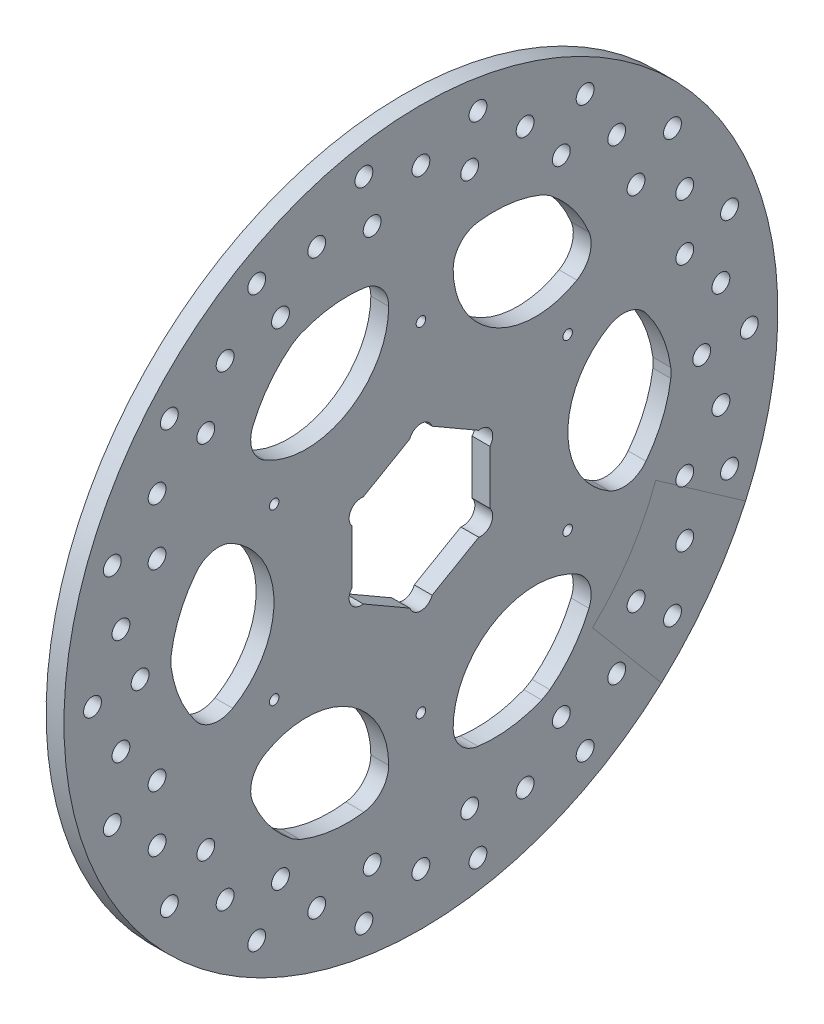
SolidWorks part; units mm, degrees
material "Gray Cast Iron (w/YS)"
ref_plane "X-Y Datum" through (0, 0, 0) normal (0, 0, 1) x (1, 0, 0)
ref_plane "X-Z Datum" through (0, 0, 0) normal (0, 1, 0) x (1, 0, 0)
ref_plane "Y-Z Datum" through (0, 0, 0) normal (1, 0, 0) x (0, 0, -1)
sketch "Sketch1" plane through (0, 0, 0) normal (1, 0, 0) x (0, 0, -1)
  circle A0 centre (0, 0) radius 95.25
  circle A1 centre (0, 0) radius 66.675
  dimension "D1" = 190.5
  dimension "D2" = 133.35
extrude "Main Rotor" add sketch "Sketch1" along normal blind 4.7625
sketch "Sketch2" plane through (4.7625, 0, 0) normal (1, 0, 0) x (0, 0, -1)
  line L0 (0, 0) -> (-50000, 0) construction
  line L1 (0, 0) -> (-93.8029, 16.54) construction
  line L4 (-82.3453, 29.9712) -> (-70.4112, 25.6276) construction
  circle A2 centre (0, 0) radius 95.25 construction
  circle A72 centre (-80.0452, 14.1141) radius 2.3813
  circle A73 centre (0, 0) radius 66.675 construction
  circle A74 centre (-82.3453, 29.9712) radius 2.3812
  circle A75 centre (-70.4112, 25.6276) radius 2.3813
  circle A76 centre (0, 0) radius 95.25 construction
  circle A77 centre (-70.3905, 40.64) radius 2.3812
  circle A78 centre (-67.1285, 56.3275) radius 2.3813
  circle A79 centre (0, 0) radius 66.675 construction
  circle A80 centre (-57.3997, 48.1641) radius 2.3813
  circle A81 centre (-52.2458, 62.2641) radius 2.3813
  circle A82 centre (-87.63, 0) radius 2.3813
  circle A83 centre (-43.815, 75.8898) radius 2.3812
  circle A84 centre (-37.465, 64.8913) radius 2.3813
  circle A85 centre (-74.93, 0) radius 2.3813
  circle A86 centre (-27.7994, 76.3782) radius 2.3812
  circle A87 centre (-15.2168, 86.2987) radius 2.3813
  circle A88 centre (-13.0115, 73.7916) radius 2.3813
  circle A89 centre (0, 81.28) radius 2.3813
  circle A90 centre (15.2168, 86.2987) radius 2.3813
  circle A91 centre (13.0115, 73.7916) radius 2.3813
  circle A92 centre (27.7994, 76.3782) radius 2.3813
  circle A93 centre (43.815, 75.8898) radius 2.3813
  circle A94 centre (37.465, 64.8913) radius 2.3813
  circle A95 centre (52.2458, 62.2641) radius 2.3813
  circle A96 centre (67.1285, 56.3275) radius 2.3813
  circle A97 centre (57.3997, 48.1641) radius 2.3813
  circle A98 centre (70.3905, 40.64) radius 2.3812
  circle A99 centre (82.3453, 29.9712) radius 2.3813
  circle A100 centre (70.4112, 25.6276) radius 2.3813
  circle A101 centre (80.0452, 14.1141) radius 2.3813
  circle A102 centre (87.63, 0) radius 2.3813
  circle A103 centre (74.93, 0) radius 2.3813
  circle A104 centre (80.0452, -14.1141) radius 2.3813
  circle A105 centre (82.3453, -29.9712) radius 2.3812
  circle A106 centre (70.4112, -25.6276) radius 2.3812
  circle A107 centre (70.3905, -40.64) radius 2.3813
  circle A108 centre (67.1285, -56.3275) radius 2.3812
  circle A109 centre (57.3997, -48.1641) radius 2.3813
  circle A110 centre (52.2458, -62.2641) radius 2.3812
  circle A111 centre (43.815, -75.8898) radius 2.3813
  circle A112 centre (37.465, -64.8913) radius 2.3813
  circle A113 centre (27.7994, -76.3782) radius 2.3813
  circle A114 centre (15.2168, -86.2987) radius 2.3813
  circle A115 centre (13.0115, -73.7916) radius 2.3812
  circle A116 centre (0, -81.28) radius 2.3812
  circle A117 centre (-15.2168, -86.2987) radius 2.3813
  circle A118 centre (-13.0115, -73.7916) radius 2.3813
  circle A119 centre (-27.7994, -76.3782) radius 2.3812
  circle A120 centre (-43.815, -75.8898) radius 2.3813
  circle A121 centre (-37.465, -64.8913) radius 2.3813
  circle A122 centre (-52.2458, -62.2641) radius 2.3813
  circle A123 centre (-67.1285, -56.3275) radius 2.3813
  circle A124 centre (-57.3997, -48.1641) radius 2.3813
  circle A125 centre (-70.3905, -40.64) radius 2.3813
  circle A126 centre (-82.3453, -29.9712) radius 2.3813
  circle A127 centre (-70.4112, -25.6276) radius 2.3813
  circle A128 centre (-80.0452, -14.1141) radius 2.3813
  point P109 (0, 0)
  dimension "D1" = 4.7625
  dimension "D2" = 12.7
  dimension "D3" = 10
  dimension "D5" = 81.28
  dimension "D4" = 87.63
  dimension "D6" = 18
extrude "Cut Slots" cut sketch "Sketch2" against normal through all
sketch "Sketch3" plane through (4.7625, 0, 0) normal (1, 0, 0) x (0, 0, -1)
  line L0 (0, 0) -> (-43301.2702, 25000) construction
  line L1 (0, 21.2491) -> (-18.4023, 10.6246)
  line L2 (-18.4023, 10.6246) -> (-18.4023, -10.6246)
  line L3 (-18.4023, -10.6246) -> (0, -21.2491)
  line L4 (0, -21.2491) -> (18.4023, -10.6246)
  line L5 (18.4023, -10.6246) -> (18.4023, 10.6246)
  line L6 (18.4023, 10.6246) -> (0, 21.2491)
  line L7 (0, 0) -> (43301.2702, 25000) construction
  line L8 (0, 0) -> (0, 50000) construction
  line L12 (9.525, -59.2994) -> (-9.525, -59.2994) construction
  line L17 (-30.6007, -53.002) -> (24969.3838, 43248.2414) construction
  line L18 (-60.783, 0) -> (49939.217, 0) construction
  line L19 (0, 0) -> (-25000, 43301.2702) construction
  arc A0 (8.6043, -53.0208) -> (15.2264, -60.5686) centre (16.2243, -53.0143) ccw
  circle A1 centre (0, 0) radius 66.675 construction
  arc A7 (-15.2264, -60.5686) -> (-32.2316, -58.3668) centre (-19.5921, -27.5182) cw
  arc A10 (15.2264, -60.5686) -> (32.2316, -58.3668) centre (19.5921, -27.5182) ccw
  arc A19 (-19.6024, -33.9524) -> (-8.6043, -53.0208) centre (-30.6006, -53.0019) cw
  arc A25 (41.6152, -33.9619) -> (44.8408, -43.4707) centre (37.7996, -40.5577) cw
  arc A26 (34.4313, -57.0968) -> (66.6629, -1.27) centre (0, 0) ccw
  arc A27 (50.2195, -19.0589) -> (60.0672, -17.0979) centre (54.0238, -12.4565) ccw
  arc A28 (19.6024, -33.9524) -> (8.6043, -53.0208) centre (30.6006, -53.0019) ccw
  arc A29 (60.0672, 17.0979) -> (50.2195, 19.0589) centre (54.0238, 12.4565) ccw
  arc A30 (-44.8408, -43.4707) -> (-34.4313, -57.0968) centre (-14.0354, -30.7264) ccw
  arc A31 (-19.6024, -33.9524) -> (-41.6152, -33.9619) centre (-30.6006, -53.0019) ccw
  arc A32 (-39.2049, 0) -> (-50.2195, -19.0589) centre (-61.2013, 0) cw
  arc A33 (-60.0672, -17.0979) -> (-66.6629, -1.27) centre (-33.6275, 3.2082) cw
  arc A34 (-60.0672, 17.0979) -> (-66.6629, 1.27) centre (-33.6275, -3.2082) ccw
  arc A35 (44.8408, 43.4707) -> (41.6152, 33.9619) centre (37.7996, 40.5577) cw
  arc A36 (-32.2316, -58.3668) -> (32.2316, -58.3668) centre (0, 0) ccw
  arc A37 (15.2264, 60.5686) -> (8.6043, 53.0208) centre (16.2243, 53.0143) ccw
  arc A38 (-8.6043, 53.0208) -> (-15.2264, 60.5686) centre (-16.2243, 53.0143) ccw
  arc A39 (-44.8408, 43.4707) -> (-41.6152, 33.9619) centre (-37.7996, 40.5577) ccw
  arc A40 (-50.2195, 19.0589) -> (-60.0672, 17.0979) centre (-54.0238, 12.4565) ccw
  arc A41 (-50.2195, -19.0589) -> (-60.0672, -17.0979) centre (-54.0238, -12.4565) cw
  arc A42 (-8.6043, -53.0208) -> (-15.2264, -60.5686) centre (-16.2243, -53.0143) cw
  arc A43 (-41.6152, -33.9619) -> (-44.8408, -43.4707) centre (-37.7996, -40.5577) ccw
  arc A44 (-39.2049, 0) -> (-50.2195, 19.0589) centre (-61.2013, 0) ccw
  arc A45 (-19.6025, 33.9524) -> (-41.6152, 33.9619) centre (-30.6007, 53.0019) cw
  arc A46 (-44.8408, 43.4707) -> (-34.4313, 57.0968) centre (-14.0354, 30.7264) cw
  arc A47 (-15.2264, 60.5686) -> (-32.2316, 58.3668) centre (-19.5921, 27.5182) ccw
  arc A48 (-19.6025, 33.9524) -> (-8.6043, 53.0208) centre (-30.6007, 53.0019) ccw
  arc A49 (19.6024, 33.9524) -> (8.6043, 53.0208) centre (30.6006, 53.0019) cw
  arc A50 (15.2264, 60.5686) -> (32.2316, 58.3668) centre (19.5921, 27.5182) cw
  arc A51 (44.8408, 43.4707) -> (34.4313, 57.0968) centre (14.0354, 30.7264) ccw
  arc A52 (19.6024, 33.9524) -> (41.6152, 33.9619) centre (30.6006, 53.0019) ccw
  arc A53 (39.2049, 0) -> (50.2195, 19.0589) centre (61.2013, 0) cw
  arc A54 (60.0672, 17.0979) -> (66.6629, 1.27) centre (33.6275, -3.2082) cw
  arc A55 (60.0672, -17.0979) -> (66.6629, -1.27) centre (33.6275, 3.2082) ccw
  arc A56 (39.2049, 0) -> (50.2195, -19.0589) centre (61.2013, 0) ccw
  arc A57 (19.6024, -33.9524) -> (41.6152, -33.9619) centre (30.6007, -53.0019) cw
  arc A58 (44.8408, -43.4707) -> (34.4313, -57.0968) centre (14.0354, -30.7264) cw
  circle A59 centre (0, 18.4551) radius 3.175
  arc A60 (-66.6629, -1.27) -> (-34.4313, -57.0968) centre (0, 0) ccw
  circle A61 centre (15.9826, 9.2276) radius 3.175
  arc A62 (-34.4313, 57.0968) -> (-66.6629, 1.27) centre (0, 0) ccw
  circle A63 centre (15.9826, -9.2276) radius 3.175
  arc A64 (32.2316, 58.3668) -> (-32.2316, 58.3668) centre (0, 0) ccw
  arc A66 (66.6629, 1.27) -> (34.4313, 57.0968) centre (0, 0) ccw
  circle A68 centre (0, -18.4551) radius 3.175
  circle A69 centre (-15.9826, -9.2276) radius 3.175
  circle A70 centre (-15.9826, 9.2276) radius 3.175
  point P34 (0, -59.2994)
  point P35 (-9.2012, 15.9369)
  point P109 (0, 0)
  point P110 (0, 0)
  point P124 (0, 0)
  dimension "D2" = 42.799
  dimension "D4" = 7.62
  dimension "D7" = 1.27
  dimension "D8" = 33.3375
  dimension "D9" = 21.9964
  dimension "D10" = 6.35
  dimension "D11" = 6.35
  dimension "D12" = 6.35
  dimension "D13" = 6.35
  dimension "D14" = 6.35
  dimension "D15" = 6.35
  dimension "D1" = 36.8046
  dimension "D3" = 6
  dimension "D5" = 2.794
  dimension "D6" = 19.05
  dimension "D16" = 2.794
  dimension "D17" = 2.794
  dimension "D18" = 2.794
  dimension "D19" = 2.794
  dimension "D20" = 2.794
extrude "Boss-Extrude2" add sketch "Sketch3" against normal up to surface (4.7625 mm away) contours A54 A66 A51 A35 A52 A49 A37 A50 A64 A47 A38 A48 A45 A39 A46 A62 A34 A40 A44 A32 A41 A33 A60 A30 A43 A31 A19 A42 A7 A36 A10 A0 A28 A57 A25 A58 A26 A55 A27 A56 A53 A29 A70 L1 A59 L6 A61 L5 A63 L4 region at (4.7625, -59.2833, -9.0788) up to face at (0, 0, 85.2488)
fillet "Fillet1" [suppressed] radius 3.175
sketch "Sketch4" plane through (0, 0, 0) normal (-1, 0, 0) x (0, 0, 1)
  circle A0 centre (0, 45.212) radius 1.27
  circle A1 centre (39.1547, 22.606) radius 1.27
  circle A2 centre (39.1547, -22.606) radius 1.27
  circle A3 centre (0, -45.212) radius 1.27
  circle A4 centre (-39.1547, -22.606) radius 1.27
  circle A5 centre (-39.1547, 22.606) radius 1.27
  point P16 (0, 0)
  dimension "D1" = 45.212
  dimension "D2" = 2.54
  dimension "D3" = 6
extrude "Cut-Extrude2" cut sketch "Sketch4" against normal through all
sketch "Sketch5" plane through (4.7625, 0, 0) normal (1, 0, 0) x (0, 0, -1)
  line L0 (0, 0) -> (-50000, 0) construction
  line L1 (0, 0) -> (-46984.631, 17101.0072) construction
  line L2 (62.654, -22.8042) -> (86.6311, -39.5931)
  line L3 (45.7933, -48.4616) -> (64.1833, -70.378)
  circle A0 centre (0, 0) radius 95.25 construction
  circle A1 centre (0, 0) radius 66.675 construction
  arc A2 (64.1833, -70.378) -> (86.6311, -39.5931) centre (0, 0) ccw
  arc A3 (45.7933, -48.4616) -> (62.654, -22.8042) centre (0, 0) ccw
  dimension "D1" = 20
  dimension "D2" = 15
  dimension "D3" = 15
  dimension "D4" = 38.1
split line "Split Line1"
ref_axis "Axis1" through (5.0006, 0, 0) along (-1, 0, 0)
